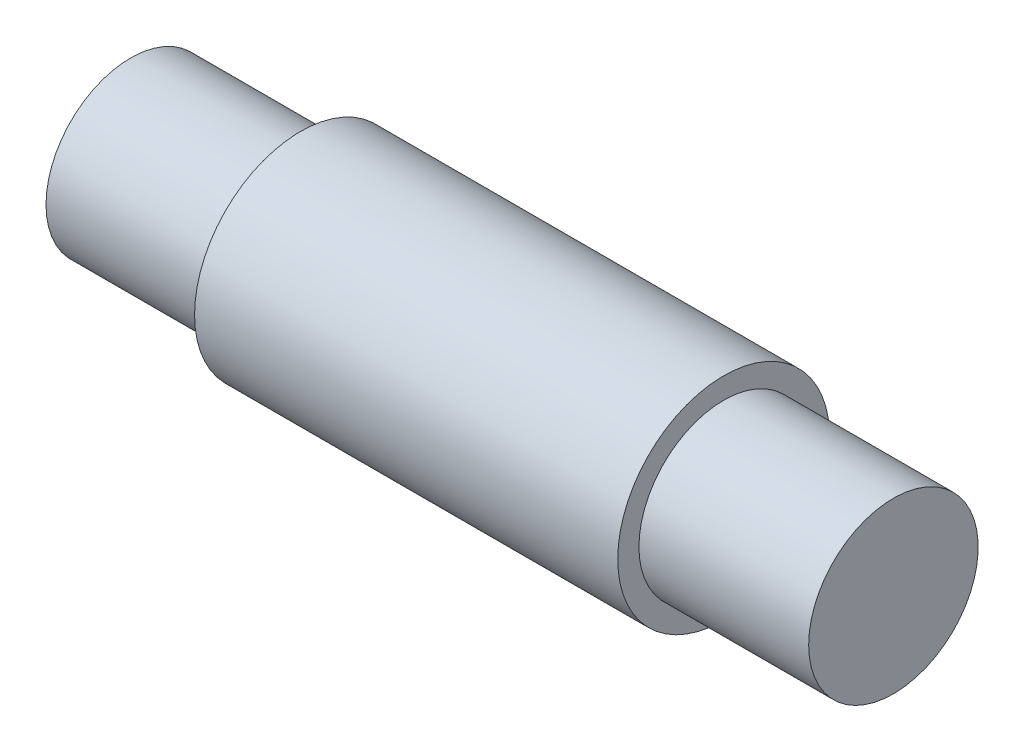
SolidWorks part; units mm, degrees
material "Alloy Steel"
ref_plane "Front Plane" through (0, 0, 0) normal (0, 0, 1) x (1, 0, 0)
ref_plane "Top Plane" through (0, 0, 0) normal (0, 1, 0) x (1, 0, 0)
ref_plane "Right Plane" through (0, 0, 0) normal (1, 0, 0) x (0, 0, -1)
sketch "Sketch1" plane through (0, 0, 0) normal (0, 0, 1) x (1, 0, 0)
  line L0 (-76.4565, 0) -> (100.0218, 0) construction
  line L1 (-14.2875, 0) -> (-14.2875, 3.175)
  line L2 (-14.2875, 3.175) -> (-7.9275, 3.175)
  line L3 (-7.9275, 3.175) -> (-7.9275, 3.9688)
  line L4 (-7.9275, 3.9688) -> (7.9275, 3.9688)
  line L5 (7.9275, 3.9688) -> (7.9275, 3.175)
  line L6 (7.9275, 3.175) -> (14.2875, 3.175)
  line L7 (14.2875, 3.175) -> (14.2875, 0)
  line L8 (14.2875, 0) -> (-14.2875, 0)
  dimension "D1" = 6.36
  dimension "D2" = 28.575
  dimension "D3" = 7.9375
  dimension "D4" = 6.35
revolve "Revolve1" add sketch "Sketch1" angle 360 about L0
